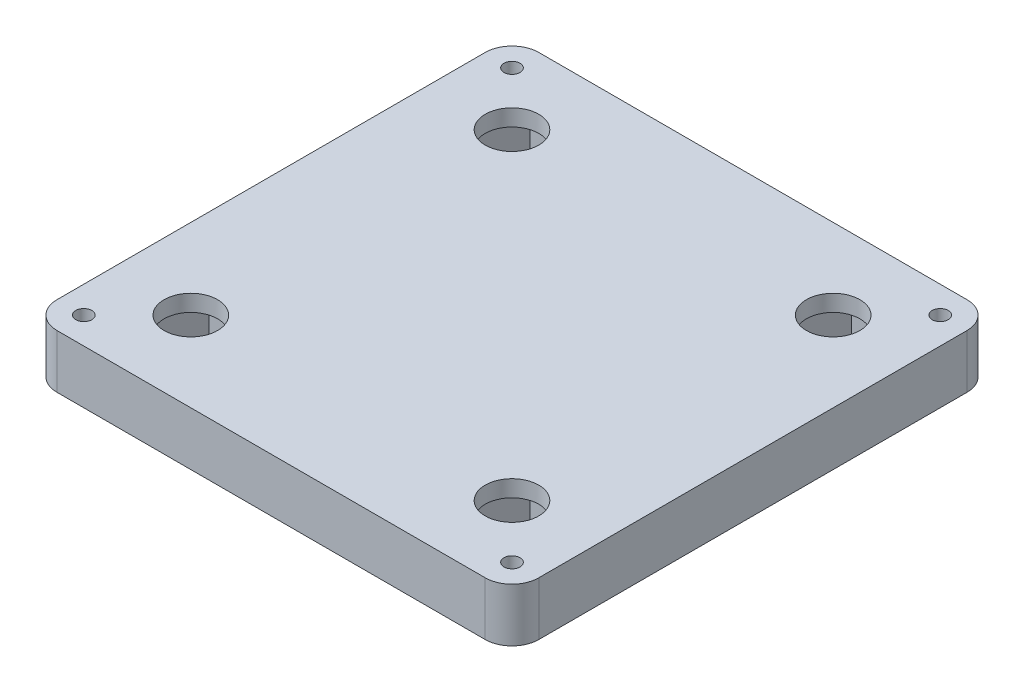
SolidWorks part; units mm, degrees
ref_plane "Front" through (0, 0, 0) normal (0, 0, 1) x (1, 0, 0)
ref_plane "Top" through (0, 0, 0) normal (0, 1, 0) x (1, 0, 0)
ref_plane "Right" through (0, 0, 0) normal (1, 0, 0) x (0, 0, -1)
sketch "Sketch1" plane through (0, 0, 0) normal (0, 1, 0) x (1, 0, 0)
  line L1 (-45, 45) -> (45, 45)
  line L2 (-45, 45) -> (-45, -45)
  line L3 (-45, -45) -> (45, -45)
  line L4 (45, 45) -> (45, -45)
  line L5 (-45, 45) -> (45, -45) construction
  line L6 (-45, -45) -> (45, 45) construction
  point P0 (0, 0)
  dimension "D1" = 90
extrude "Boss-Extrude1" add sketch "Sketch1" along normal blind 10
sketch "Sketch2" plane through (0, 0, 0) normal (0, -1, 0) x (1, 0, 0)
  line L1 (9.2376, 0) -> (4.6188, 8)
  line L2 (4.6188, 8) -> (-4.6188, 8)
  line L3 (-4.6188, 8) -> (-9.2376, 0)
  line L4 (-9.2376, 0) -> (-4.6188, -8)
  line L5 (-4.6188, -8) -> (4.6188, -8)
  line L6 (4.6188, -8) -> (9.2376, 0)
  line L12 (-45, 45) -> (45, -45) construction
  line L19 (-15.2868, 8.7548) -> (-8.7548, 15.2868)
  line L20 (-8.7548, 15.2868) -> (-11.1457, 24.2096)
  line L21 (-11.1457, 24.2096) -> (-20.0685, 26.6005)
  line L22 (-20.0685, 26.6005) -> (-26.6005, 20.0685)
  line L23 (-26.6005, 20.0685) -> (-24.2096, 11.1457)
  line L24 (-24.2096, 11.1457) -> (-15.2868, 8.7548)
  line L25 (20.0685, -26.6005) -> (26.6005, -20.0685)
  line L26 (26.6005, -20.0685) -> (24.2096, -11.1457)
  line L27 (24.2096, -11.1457) -> (15.2868, -8.7548)
  line L28 (15.2868, -8.7548) -> (8.7548, -15.2868)
  line L29 (8.7548, -15.2868) -> (11.1457, -24.2096)
  line L30 (11.1457, -24.2096) -> (20.0685, -26.6005)
  line L31 (-45, -45) -> (-45, 45) construction
  line L32 (45, 45) -> (45, -45) construction
  line L33 (45, -45) -> (-45, -45) construction
  line L34 (-45, 45) -> (45, 45) construction
  circle A0 centre (0, 0) radius 8 construction
  arc A1 (17.6777, -17.6777) -> (-17.6777, 17.6777) centre (0, 0) ccw construction
  arc A2 (23.3345, -23.3345) -> (-23.3345, 23.3345) centre (0, 0) ccw
  arc A3 (12.0208, -12.0208) -> (-12.0208, 12.0208) centre (0, 0) ccw
  arc A4 (12.0208, -12.0208) -> (23.3345, -23.3345) centre (17.6777, -17.6777) ccw
  arc A5 (-23.3345, 23.3345) -> (-12.0208, 12.0208) centre (-17.6777, 17.6777) ccw
  circle A6 centre (-17.6777, 17.6777) radius 8 construction
  circle A7 centre (17.6777, -17.6777) radius 8 construction
  point P11 (17.6777, 17.6777)
  dimension "D2" = 25
  dimension "D3" = 8
  dimension "D1" = 16
extrude "Cut-Extrude1" cut sketch "Sketch2" against normal blind 6.9 contours L5 L6 L1 L2 L3 L4 | A3 L28 L27 L26 A2 L21 L20 L19 | L28 A4 A2 L26 L27 | A2 A5 L19 L20 L21 | A5 L22 L23 | A5 L24 L19 | A5 L23 L24 | A4 L28 L29 | A4 L29 L30 | A4 L30 L25 region at (0, 0, 0) region at (-15.5376, 0, 9.6909) region at (-17.4791, 0, 17.848) region at (13.5756, 0, 13.5756) region at (-23.5244, 0, 11.831) region at (9.6909, 0, -15.5376) region at (17.848, 0, -17.4791) region at (-25.6644, 0, 19.8177) region at (11.831, 0, -23.5244) region at (19.8177, 0, -25.6644)
sketch "Sketch3" plane through (0, 10, 0) normal (0, 1, 0) x (1, 0, 0)
  line L1 (-40, -40) -> (40, -40) construction
  line L2 (-40, -40) -> (-40, 40) construction
  line L3 (-40, 40) -> (40, 40) construction
  line L4 (40, -40) -> (40, 40) construction
  line L5 (-40, -40) -> (40, 40) construction
  line L6 (-40, 40) -> (40, -40) construction
  circle A0 centre (-40, 40) radius 1.5
  circle A1 centre (40, 40) radius 1.5
  circle A2 centre (40, -40) radius 1.5
  circle A3 centre (-40, -40) radius 1.5
  point P0 (0, 0)
  dimension "D2" = 3
  dimension "D1" = 80
extrude "Cut-Extrude2" cut sketch "Sketch3" against normal through all
sketch "Sketch4" plane through (0, 10, 0) normal (0, 1, 0) x (1, 0, 0)
  line L1 (-30, -30) -> (30, -30) construction
  line L2 (-30, -30) -> (-30, 30) construction
  line L3 (-30, 30) -> (30, 30) construction
  line L4 (30, -30) -> (30, 30) construction
  line L5 (-30, -30) -> (30, 30) construction
  line L6 (-30, 30) -> (30, -30) construction
  circle A0 centre (-30, 30) radius 5
  circle A1 centre (30, 30) radius 5
  circle A2 centre (30, -30) radius 5
  circle A3 centre (-30, -30) radius 5
  point P0 (0, 0)
  dimension "D2" = 10
  dimension "D1" = 60
extrude "Cut-Extrude3" cut sketch "Sketch4" against normal through all
sketch "Sketch6" plane through (0, 0, 0) normal (0, -1, 0) x (1, 0, 0)
  line L1 (-25.3812, 22) -> (-20.7624, 30)
  line L2 (-20.7624, 30) -> (-25.3812, 38)
  line L3 (-25.3812, 38) -> (-34.6188, 38)
  line L4 (-34.6188, 38) -> (-39.2376, 30)
  line L5 (-39.2376, 30) -> (-34.6188, 22)
  line L6 (-34.6188, 22) -> (-25.3812, 22)
  line L7 (34.6188, 22) -> (39.2376, 30)
  line L8 (39.2376, 30) -> (34.6188, 38)
  line L9 (34.6188, 38) -> (25.3812, 38)
  line L10 (25.3812, 38) -> (20.7624, 30)
  line L11 (20.7624, 30) -> (25.3812, 22)
  line L12 (25.3812, 22) -> (34.6188, 22)
  line L13 (34.6188, -38) -> (39.2376, -30)
  line L14 (39.2376, -30) -> (34.6188, -22)
  line L15 (34.6188, -22) -> (25.3812, -22)
  line L16 (25.3812, -22) -> (20.7624, -30)
  line L17 (20.7624, -30) -> (25.3812, -38)
  line L18 (25.3812, -38) -> (34.6188, -38)
  line L19 (-20.7624, -30) -> (-25.3812, -22)
  line L20 (-25.3812, -22) -> (-34.6188, -22)
  line L21 (-34.6188, -22) -> (-39.2376, -30)
  line L22 (-39.2376, -30) -> (-34.6188, -38)
  line L23 (-34.6188, -38) -> (-25.3812, -38)
  line L24 (-25.3812, -38) -> (-20.7624, -30)
  circle A0 centre (-30, 30) radius 8 construction
  circle A1 centre (30, 30) radius 8 construction
  circle A2 centre (30, -30) radius 8 construction
  circle A3 centre (-30, -30) radius 8 construction
  dimension "D1" = 16
extrude "Cut-Extrude4" cut sketch "Sketch6" against normal blind 6.9
fillet "Fillet1" radius 5 4 edges at (-45, 5, 45) (-45, 5, -45) (45, 5, 45) (45, 5, -45)
